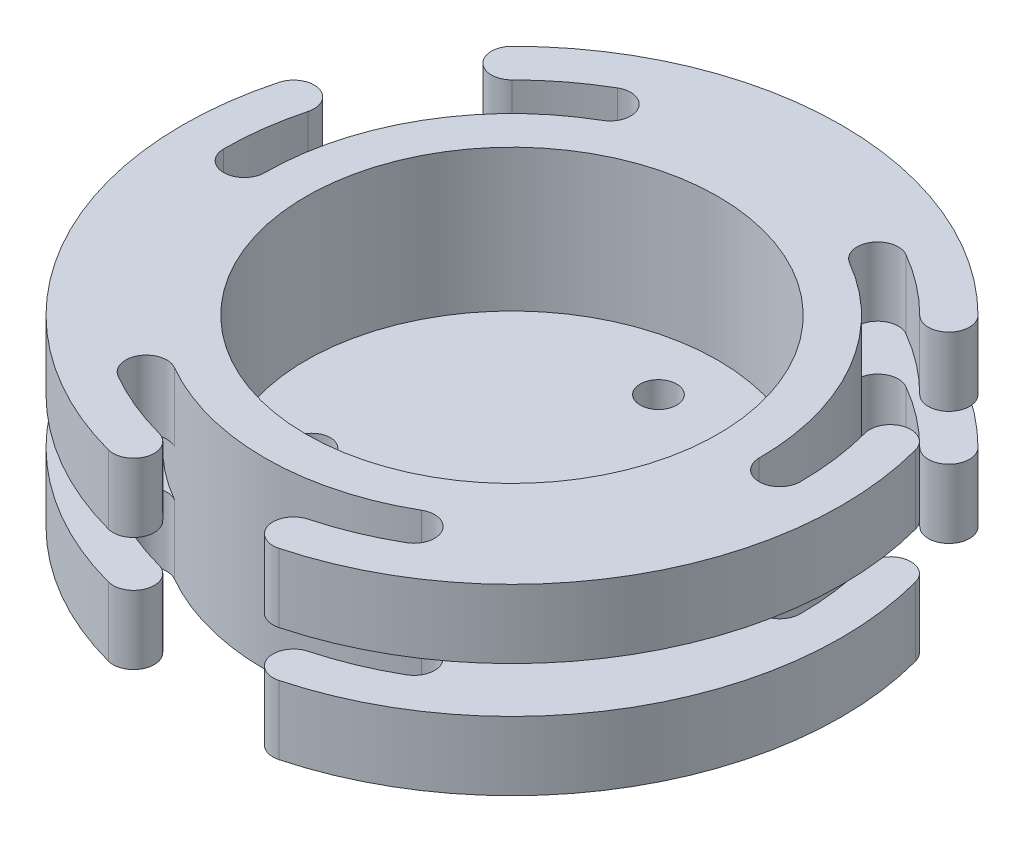
SolidWorks part; units mm, degrees
material "Alliage 1060"
ref_plane "Plan de face" through (0, 0, 0) normal (0, 0, 1) x (1, 0, 0)
ref_plane "Plan de dessus" through (0, 0, 0) normal (0, 1, 0) x (1, 0, 0)
ref_plane "Plan de droite" through (0, 0, 0) normal (1, 0, 0) x (0, 0, -1)
sketch "Esquisse1" plane through (0, 0, 0) normal (0, 1, 0) x (1, 0, 0)
  circle A0 centre (0, 0) radius 22.5
  circle A1 centre (0, 0) radius 40 construction
  circle A2 centre (0, 0) radius 36 construction
  circle A3 centre (0, 0) radius 31.5
  circle A4 centre (0, 0) radius 27 construction
  dimension "D1" = 45
  dimension "D2" = 80
  dimension "D3" = 72
  dimension "D4" = 63
  dimension "D5" = 54
extrude "Boss.-Extru.1" add sketch "Esquisse1" along normal blind 20
sketch "Esquisse2" plane through (0, 20, 0) normal (0, 1, 0) x (1, 0, 0)
  line L0 (-14.625, 25.3312) -> (0, 0) construction
  line L1 (0, 0) -> (-29.25, 0) construction
  line L2 (0, 0) -> (0, 31.5) construction
  arc A0 (-29.25, 0) -> (-14.625, 25.3312) centre (0, 0) cw construction
  arc A1 (-15.75, 27.2798) -> (-31.5, 0) centre (0, 0) ccw
  arc A2 (-13.5, 23.3827) -> (-27, 0) centre (0, 0) ccw
  arc A3 (-13.5, 23.3827) -> (-15.75, 27.2798) centre (-14.625, 25.3312) ccw
  arc A4 (-31.5, 0) -> (-27, 0) centre (-29.25, 0) ccw
  circle A5 centre (0, 0) radius 31.5 construction
  arc A6 (14.625, 25.3312) -> (29.25, 0) centre (0, 0) cw construction
  arc A7 (31.5, 0) -> (15.75, 27.2798) centre (0, 0) ccw
  arc A8 (27, 0) -> (13.5, 23.3827) centre (0, 0) ccw
  arc A9 (27, 0) -> (31.5, 0) centre (29.25, 0) ccw
  arc A10 (15.75, 27.2798) -> (13.5, 23.3827) centre (14.625, 25.3312) ccw
  arc A11 (14.625, -25.3312) -> (-14.625, -25.3312) centre (0, 0) cw construction
  arc A12 (-15.75, -27.2798) -> (15.75, -27.2798) centre (0, 0) ccw
  arc A13 (-13.5, -23.3827) -> (13.5, -23.3827) centre (0, 0) ccw
  arc A14 (-13.5, -23.3827) -> (-15.75, -27.2798) centre (-14.625, -25.3312) ccw
  arc A15 (15.75, -27.2798) -> (13.5, -23.3827) centre (14.625, -25.3312) ccw
  point P4 (-25.3312, 14.625)
  point P21 (25.3312, 14.625)
  point P28 (0, -29.25)
  point P33 (0, 0)
  dimension "D1" = 2.25
  dimension "D2" = 60
  dimension "D3" = 30
  dimension "D4" = 3
extrude "Enlèv. mat.-Extru.1" cut sketch "Esquisse2" against normal through all
sketch "Esquisse3" plane through (0, 20, 0) normal (0, 1, 0) x (1, 0, 0)
  line L0 (0, 33.75) -> (0, 0) construction
  line L1 (-23.8649, 23.8649) -> (0, 0) construction
  arc A0 (-23.8649, 23.8649) -> (23.8649, 23.8649) centre (0, 0) cw construction
  arc A1 (25.4558, 25.4558) -> (-25.4558, 25.4558) centre (0, 0) ccw
  arc A2 (22.2739, 22.2739) -> (-22.2739, 22.2739) centre (0, 0) ccw
  arc A3 (22.2739, 22.2739) -> (25.4558, 25.4558) centre (23.8649, 23.8649) ccw
  arc A4 (-25.4558, 25.4558) -> (-22.2739, 22.2739) centre (-23.8649, 23.8649) ccw
  arc A5 (15.75, 27.2798) -> (-15.75, 27.2798) centre (0, 0) ccw construction
  arc A6 (32.6, 8.7351) -> (8.7351, -32.6) centre (0, 0) cw construction
  arc A7 (9.3175, -34.7733) -> (34.7733, 9.3175) centre (0, 0) ccw
  arc A8 (8.1528, -30.4267) -> (30.4267, 8.1528) centre (0, 0) ccw
  arc A9 (8.1528, -30.4267) -> (9.3175, -34.7733) centre (8.7351, -32.6) ccw
  arc A10 (34.7733, 9.3175) -> (30.4267, 8.1528) centre (32.6, 8.7351) ccw
  arc A11 (-8.7351, -32.6) -> (-32.6, 8.7351) centre (0, 0) cw construction
  arc A12 (-34.7733, 9.3175) -> (-9.3175, -34.7733) centre (0, 0) ccw
  arc A13 (-30.4267, 8.1528) -> (-8.1528, -30.4267) centre (0, 0) ccw
  arc A14 (-30.4267, 8.1528) -> (-34.7733, 9.3175) centre (-32.6, 8.7351) ccw
  arc A15 (-9.3175, -34.7733) -> (-8.1528, -30.4267) centre (-8.7351, -32.6) ccw
  point P4 (0, 33.75)
  point P19 (29.2284, -16.875)
  point P26 (-29.2284, -16.875)
  point P31 (0, 0)
  dimension "D1" = 2.25
  dimension "D2" = 45
extrude "Boss.-Extru.2" add sketch "Esquisse3" against normal up to surface (20 mm away) up to face at (0, 0, 0)
sketch "Esquisse4" plane through (0, 0, 0) normal (0, -1, 0) x (1, 0, 0)
  circle A0 centre (0, 0) radius 22.5
extrude "Boss.-Extru.3" add sketch "Esquisse4" against normal blind 4.5
sketch "Esquisse5" plane through (0, 4.5, 0) normal (0, 1, 0) x (1, 0, 0)
  line L0 (0, 0) -> (0, 16) construction
  circle A0 centre (0, 16) radius 2
  circle A1 centre (13.8564, -8) radius 2
  circle A2 centre (-13.8564, -8) radius 2
  point P12 (0, 0)
  dimension "D2" = 4
  dimension "D1" = 16
  dimension "D3" = 3
extrude "Enlèv. mat.-Extru.2" cut sketch "Esquisse5" against normal up to next
sketch "Esquisse6" plane through (0, 0, 0) normal (1, 0, 0) x (0, 0, -1)
  line L0 (36, 10) -> (0, 10) construction
  line L1 (36, 12.5) -> (27, 12.5)
  line L2 (36, 12.5) -> (36, 7.5)
  line L3 (36, 7.5) -> (27, 7.5)
  line L4 (27, 12.5) -> (27, 7.5)
  line L5 (0, 10) -> (0, 0) construction
  dimension "D1" = 10
  dimension "D2" = 9
  dimension "D3" = 36
  dimension "D4" = 5
revolve "Enlèvement de matière-Révolution1" cut sketch "Esquisse6" angle 360 about L5
